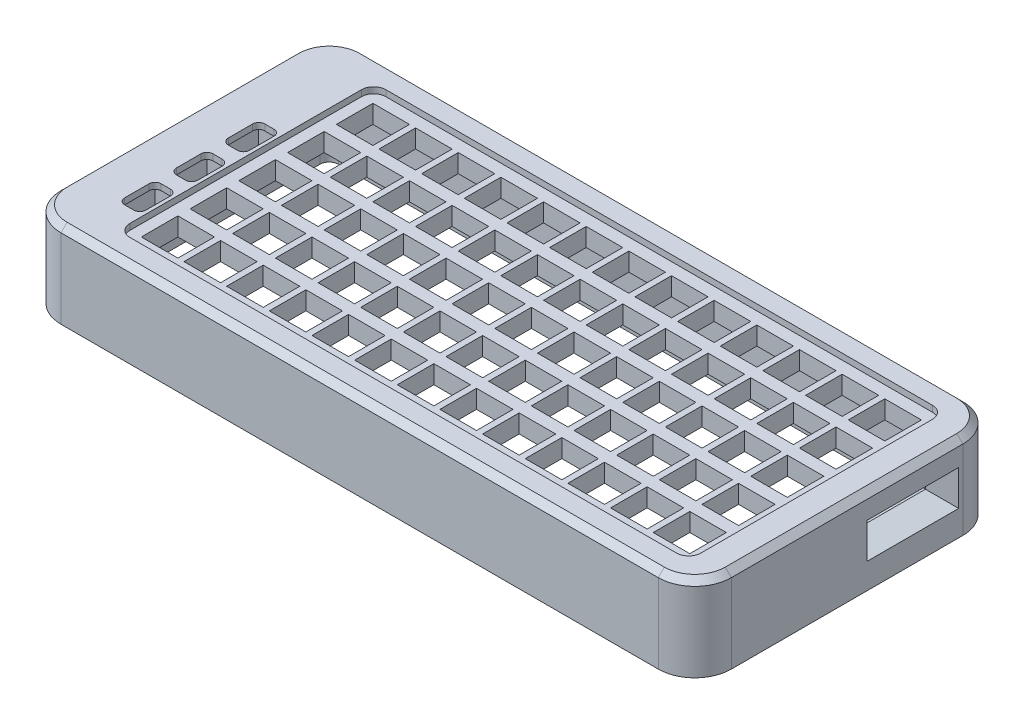
SolidWorks part; units mm, degrees
ref_plane "前视基准面" through (0, 0, 0) normal (0, 0, 1) x (1, 0, 0)
ref_plane "上视基准面" through (0, 0, 0) normal (0, 1, 0) x (1, 0, 0)
ref_plane "右视基准面" through (0, 0, 0) normal (1, 0, 0) x (0, 0, -1)
other "Configuration Table"
sketch "草图1" plane through (0, 0, 0) normal (0, 1, 0) x (1, 0, 0)
  line L1 (-55, -25) -> (55, -25)
  line L2 (-55, -25) -> (-55, 25)
  line L3 (-55, 25) -> (55, 25)
  line L4 (55, -25) -> (55, 25)
  line L5 (-55, -25) -> (55, 25) construction
  line L6 (-55, 25) -> (55, -25) construction
  point P0 (0, 0)
  dimension "D1" = 50
  dimension "D2" = 110
extrude "凸台-拉伸1" add sketch "草图1" along normal blind 3
sketch "草图2" plane through (0, 0, 0) normal (0, -1, 0) x (1, 0, 0)
  line L0 (46.3251, 14.2) -> (44.0251, 17.8) construction
  line L1 (48.1751, 11) -> (48.1751, 5)
  line L2 (48.1751, 19) -> (42.1751, 19)
  line L3 (48.1751, 19) -> (48.1751, 13)
  line L4 (48.1751, 13) -> (42.1751, 13)
  line L5 (42.1751, 19) -> (42.1751, 13)
  line L6 (48.1751, 19) -> (42.1751, 13) construction
  line L7 (48.1751, 13) -> (42.1751, 19) construction
  line L8 (48.1751, 5) -> (42.1751, 5)
  line L9 (42.1751, 11) -> (42.1751, 5)
  line L10 (48.1751, 11) -> (42.1751, 11)
  line L11 (48.1751, 3) -> (48.1751, -3)
  line L12 (48.1751, -3) -> (42.1751, -3)
  line L13 (42.1751, 3) -> (42.1751, -3)
  line L14 (48.1751, 3) -> (42.1751, 3)
  line L15 (48.1751, -5) -> (48.1751, -11)
  line L16 (48.1751, -11) -> (42.1751, -11)
  line L17 (42.1751, -5) -> (42.1751, -11)
  line L18 (48.1751, -5) -> (42.1751, -5)
  line L19 (48.1751, -13) -> (48.1751, -19)
  line L20 (48.1751, -19) -> (42.1751, -19)
  line L21 (42.1751, -13) -> (42.1751, -19)
  line L22 (48.1751, -13) -> (42.1751, -13)
  line L23 (41.1751, 11) -> (41.1751, 5)
  line L24 (41.1751, 5) -> (35.1751, 5)
  line L25 (35.1751, 11) -> (35.1751, 5)
  line L26 (41.1751, 11) -> (35.1751, 11)
  line L27 (41.1751, 3) -> (41.1751, -3)
  line L28 (41.1751, -3) -> (35.1751, -3)
  line L29 (35.1751, 3) -> (35.1751, -3)
  line L30 (41.1751, 3) -> (35.1751, 3)
  line L31 (41.1751, -5) -> (41.1751, -11)
  line L32 (41.1751, -11) -> (35.1751, -11)
  line L33 (35.1751, -5) -> (35.1751, -11)
  line L34 (41.1751, -5) -> (35.1751, -5)
  line L35 (41.1751, -13) -> (41.1751, -19)
  line L36 (41.1751, -19) -> (35.1751, -19)
  line L37 (35.1751, -13) -> (35.1751, -19)
  line L38 (41.1751, -13) -> (35.1751, -13)
  line L39 (34.1751, 11) -> (34.1751, 5)
  line L40 (34.1751, 5) -> (28.1751, 5)
  line L41 (28.1751, 11) -> (28.1751, 5)
  line L42 (34.1751, 11) -> (28.1751, 11)
  line L43 (34.1751, 3) -> (34.1751, -3)
  line L44 (34.1751, -3) -> (28.1751, -3)
  line L45 (28.1751, 3) -> (28.1751, -3)
  line L46 (34.1751, 3) -> (28.1751, 3)
  line L47 (34.1751, -5) -> (34.1751, -11)
  line L48 (34.1751, -11) -> (28.1751, -11)
  line L49 (28.1751, -5) -> (28.1751, -11)
  line L50 (34.1751, -5) -> (28.1751, -5)
  line L51 (34.1751, -13) -> (34.1751, -19)
  line L52 (34.1751, -19) -> (28.1751, -19)
  line L53 (28.1751, -13) -> (28.1751, -19)
  line L54 (34.1751, -13) -> (28.1751, -13)
  line L55 (27.1751, 11) -> (27.1751, 5)
  line L56 (27.1751, 5) -> (21.1751, 5)
  line L57 (21.1751, 11) -> (21.1751, 5)
  line L58 (27.1751, 11) -> (21.1751, 11)
  line L59 (27.1751, 3) -> (27.1751, -3)
  line L60 (27.1751, -3) -> (21.1751, -3)
  line L61 (21.1751, 3) -> (21.1751, -3)
  line L62 (27.1751, 3) -> (21.1751, 3)
  line L63 (27.1751, -5) -> (27.1751, -11)
  line L64 (27.1751, -11) -> (21.1751, -11)
  line L65 (21.1751, -5) -> (21.1751, -11)
  line L66 (27.1751, -5) -> (21.1751, -5)
  line L67 (27.1751, -13) -> (27.1751, -19)
  line L68 (27.1751, -19) -> (21.1751, -19)
  line L69 (21.1751, -13) -> (21.1751, -19)
  line L70 (27.1751, -13) -> (21.1751, -13)
  line L71 (20.1751, 11) -> (20.1751, 5)
  line L72 (20.1751, 5) -> (14.1751, 5)
  line L73 (14.1751, 11) -> (14.1751, 5)
  line L74 (20.1751, 11) -> (14.1751, 11)
  line L75 (20.1751, 3) -> (20.1751, -3)
  line L76 (20.1751, -3) -> (14.1751, -3)
  line L77 (14.1751, 3) -> (14.1751, -3)
  line L78 (20.1751, 3) -> (14.1751, 3)
  line L79 (20.1751, -5) -> (20.1751, -11)
  line L80 (20.1751, -11) -> (14.1751, -11)
  line L81 (14.1751, -5) -> (14.1751, -11)
  line L82 (20.1751, -5) -> (14.1751, -5)
  line L83 (20.1751, -13) -> (20.1751, -19)
  line L84 (20.1751, -19) -> (14.1751, -19)
  line L85 (14.1751, -13) -> (14.1751, -19)
  line L86 (20.1751, -13) -> (14.1751, -13)
  line L87 (13.1751, 11) -> (13.1751, 5)
  line L88 (13.1751, 5) -> (7.1751, 5)
  line L89 (7.1751, 11) -> (7.1751, 5)
  line L90 (13.1751, 11) -> (7.1751, 11)
  line L91 (13.1751, 3) -> (13.1751, -3)
  line L92 (13.1751, -3) -> (7.1751, -3)
  line L93 (7.1751, 3) -> (7.1751, -3)
  line L94 (13.1751, 3) -> (7.1751, 3)
  line L95 (13.1751, -5) -> (13.1751, -11)
  line L96 (13.1751, -11) -> (7.1751, -11)
  line L97 (7.1751, -5) -> (7.1751, -11)
  line L98 (13.1751, -5) -> (7.1751, -5)
  line L99 (13.1751, -13) -> (13.1751, -19)
  line L100 (13.1751, -19) -> (7.1751, -19)
  line L101 (7.1751, -13) -> (7.1751, -19)
  line L102 (13.1751, -13) -> (7.1751, -13)
  line L103 (6.1751, 11) -> (6.1751, 5)
  line L104 (6.1751, 5) -> (0.1751, 5)
  line L105 (0.1751, 11) -> (0.1751, 5)
  line L106 (6.1751, 11) -> (0.1751, 11)
  line L107 (6.1751, 3) -> (6.1751, -3)
  line L108 (6.1751, -3) -> (0.1751, -3)
  line L109 (0.1751, 3) -> (0.1751, -3)
  line L110 (6.1751, 3) -> (0.1751, 3)
  line L111 (6.1751, -5) -> (6.1751, -11)
  line L112 (6.1751, -11) -> (0.1751, -11)
  line L113 (0.1751, -5) -> (0.1751, -11)
  line L114 (6.1751, -5) -> (0.1751, -5)
  line L115 (6.1751, -13) -> (6.1751, -19)
  line L116 (6.1751, -19) -> (0.1751, -19)
  line L117 (0.1751, -13) -> (0.1751, -19)
  line L118 (6.1751, -13) -> (0.1751, -13)
  line L119 (-0.8249, 11) -> (-0.8249, 5)
  line L120 (-0.8249, 5) -> (-6.8249, 5)
  line L121 (-6.8249, 11) -> (-6.8249, 5)
  line L122 (-0.8249, 11) -> (-6.8249, 11)
  line L123 (-0.8249, 3) -> (-0.8249, -3)
  line L124 (-0.8249, -3) -> (-6.8249, -3)
  line L125 (-6.8249, 3) -> (-6.8249, -3)
  line L126 (-0.8249, 3) -> (-6.8249, 3)
  line L127 (-0.8249, -5) -> (-0.8249, -11)
  line L128 (-0.8249, -11) -> (-6.8249, -11)
  line L129 (-6.8249, -5) -> (-6.8249, -11)
  line L130 (-0.8249, -5) -> (-6.8249, -5)
  line L131 (-0.8249, -13) -> (-0.8249, -19)
  line L132 (-0.8249, -19) -> (-6.8249, -19)
  line L133 (-6.8249, -13) -> (-6.8249, -19)
  line L134 (-0.8249, -13) -> (-6.8249, -13)
  line L135 (-7.8249, 11) -> (-7.8249, 5)
  line L136 (-7.8249, 5) -> (-13.8249, 5)
  line L137 (-13.8249, 11) -> (-13.8249, 5)
  line L138 (-7.8249, 11) -> (-13.8249, 11)
  line L139 (-7.8249, 3) -> (-7.8249, -3)
  line L140 (-7.8249, -3) -> (-13.8249, -3)
  line L141 (-13.8249, 3) -> (-13.8249, -3)
  line L142 (-7.8249, 3) -> (-13.8249, 3)
  line L143 (-7.8249, -5) -> (-7.8249, -11)
  line L144 (-7.8249, -11) -> (-13.8249, -11)
  line L145 (-13.8249, -5) -> (-13.8249, -11)
  line L146 (-7.8249, -5) -> (-13.8249, -5)
  line L147 (-7.8249, -13) -> (-7.8249, -19)
  line L148 (-7.8249, -19) -> (-13.8249, -19)
  line L149 (-13.8249, -13) -> (-13.8249, -19)
  line L150 (-7.8249, -13) -> (-13.8249, -13)
  line L151 (-14.8249, 11) -> (-14.8249, 5)
  line L152 (-14.8249, 5) -> (-20.8249, 5)
  line L153 (-20.8249, 11) -> (-20.8249, 5)
  line L154 (-14.8249, 11) -> (-20.8249, 11)
  line L155 (-14.8249, 3) -> (-14.8249, -3)
  line L156 (-14.8249, -3) -> (-20.8249, -3)
  line L157 (-20.8249, 3) -> (-20.8249, -3)
  line L158 (-14.8249, 3) -> (-20.8249, 3)
  line L159 (-14.8249, -5) -> (-14.8249, -11)
  line L160 (-14.8249, -11) -> (-20.8249, -11)
  line L161 (-20.8249, -5) -> (-20.8249, -11)
  line L162 (-14.8249, -5) -> (-20.8249, -5)
  line L163 (-14.8249, -13) -> (-14.8249, -19)
  line L164 (-14.8249, -19) -> (-20.8249, -19)
  line L165 (-20.8249, -13) -> (-20.8249, -19)
  line L166 (-14.8249, -13) -> (-20.8249, -13)
  line L167 (-21.8249, 11) -> (-21.8249, 5)
  line L168 (-21.8249, 5) -> (-27.8249, 5)
  line L169 (-27.8249, 11) -> (-27.8249, 5)
  line L170 (-21.8249, 11) -> (-27.8249, 11)
  line L171 (-21.8249, 3) -> (-21.8249, -3)
  line L172 (-21.8249, -3) -> (-27.8249, -3)
  line L173 (-27.8249, 3) -> (-27.8249, -3)
  line L174 (-21.8249, 3) -> (-27.8249, 3)
  line L175 (-21.8249, -5) -> (-21.8249, -11)
  line L176 (-21.8249, -11) -> (-27.8249, -11)
  line L177 (-27.8249, -5) -> (-27.8249, -11)
  line L178 (-21.8249, -5) -> (-27.8249, -5)
  line L179 (-21.8249, -13) -> (-21.8249, -19)
  line L180 (-21.8249, -19) -> (-27.8249, -19)
  line L181 (-27.8249, -13) -> (-27.8249, -19)
  line L182 (-21.8249, -13) -> (-27.8249, -13)
  line L183 (-28.8249, 11) -> (-28.8249, 5)
  line L184 (-28.8249, 5) -> (-34.8249, 5)
  line L185 (-34.8249, 11) -> (-34.8249, 5)
  line L186 (-28.8249, 11) -> (-34.8249, 11)
  line L187 (-28.8249, 3) -> (-28.8249, -3)
  line L188 (-28.8249, -3) -> (-34.8249, -3)
  line L189 (-34.8249, 3) -> (-34.8249, -3)
  line L190 (-28.8249, 3) -> (-34.8249, 3)
  line L191 (-28.8249, -5) -> (-28.8249, -11)
  line L192 (-28.8249, -11) -> (-34.8249, -11)
  line L193 (-34.8249, -5) -> (-34.8249, -11)
  line L194 (-28.8249, -5) -> (-34.8249, -5)
  line L195 (-28.8249, -13) -> (-28.8249, -19)
  line L196 (-28.8249, -19) -> (-34.8249, -19)
  line L197 (-34.8249, -13) -> (-34.8249, -19)
  line L198 (-28.8249, -13) -> (-34.8249, -13)
  line L199 (-35.8249, 11) -> (-35.8249, 5)
  line L200 (-35.8249, 5) -> (-41.8249, 5)
  line L201 (-41.8249, 11) -> (-41.8249, 5)
  line L202 (-35.8249, 11) -> (-41.8249, 11)
  line L203 (-35.8249, 3) -> (-35.8249, -3)
  line L204 (-35.8249, -3) -> (-41.8249, -3)
  line L205 (-41.8249, 3) -> (-41.8249, -3)
  line L206 (-35.8249, 3) -> (-41.8249, 3)
  line L207 (-35.8249, -5) -> (-35.8249, -11)
  line L208 (-35.8249, -11) -> (-41.8249, -11)
  line L209 (-41.8249, -5) -> (-41.8249, -11)
  line L210 (-35.8249, -5) -> (-41.8249, -5)
  line L211 (-35.8249, -13) -> (-35.8249, -19)
  line L212 (-35.8249, -19) -> (-41.8249, -19)
  line L213 (-41.8249, -13) -> (-41.8249, -19)
  line L214 (-35.8249, -13) -> (-41.8249, -13)
  line L215 (41.1751, 19) -> (41.1751, 13)
  line L216 (41.1751, 13) -> (35.1751, 13)
  line L217 (35.1751, 19) -> (35.1751, 13)
  line L218 (41.1751, 19) -> (35.1751, 19)
  line L219 (34.1751, 19) -> (34.1751, 13)
  line L220 (34.1751, 13) -> (28.1751, 13)
  line L221 (28.1751, 19) -> (28.1751, 13)
  line L222 (34.1751, 19) -> (28.1751, 19)
  line L223 (27.1751, 19) -> (27.1751, 13)
  line L224 (27.1751, 13) -> (21.1751, 13)
  line L225 (21.1751, 19) -> (21.1751, 13)
  line L226 (27.1751, 19) -> (21.1751, 19)
  line L227 (20.1751, 19) -> (20.1751, 13)
  line L228 (20.1751, 13) -> (14.1751, 13)
  line L229 (14.1751, 19) -> (14.1751, 13)
  line L230 (20.1751, 19) -> (14.1751, 19)
  line L231 (13.1751, 19) -> (13.1751, 13)
  line L232 (13.1751, 13) -> (7.1751, 13)
  line L233 (7.1751, 19) -> (7.1751, 13)
  line L234 (13.1751, 19) -> (7.1751, 19)
  line L235 (6.1751, 19) -> (6.1751, 13)
  line L236 (6.1751, 13) -> (0.1751, 13)
  line L237 (0.1751, 19) -> (0.1751, 13)
  line L238 (6.1751, 19) -> (0.1751, 19)
  line L239 (-0.8249, 19) -> (-0.8249, 13)
  line L240 (-0.8249, 13) -> (-6.8249, 13)
  line L241 (-6.8249, 19) -> (-6.8249, 13)
  line L242 (-0.8249, 19) -> (-6.8249, 19)
  line L243 (-7.8249, 19) -> (-7.8249, 13)
  line L244 (-7.8249, 13) -> (-13.8249, 13)
  line L245 (-13.8249, 19) -> (-13.8249, 13)
  line L246 (-7.8249, 19) -> (-13.8249, 19)
  line L247 (-14.8249, 19) -> (-14.8249, 13)
  line L248 (-14.8249, 13) -> (-20.8249, 13)
  line L249 (-20.8249, 19) -> (-20.8249, 13)
  line L250 (-14.8249, 19) -> (-20.8249, 19)
  line L251 (-21.8249, 19) -> (-21.8249, 13)
  line L252 (-21.8249, 13) -> (-27.8249, 13)
  line L253 (-27.8249, 19) -> (-27.8249, 13)
  line L254 (-21.8249, 19) -> (-27.8249, 19)
  line L255 (-28.8249, 19) -> (-28.8249, 13)
  line L256 (-28.8249, 13) -> (-34.8249, 13)
  line L257 (-34.8249, 19) -> (-34.8249, 13)
  line L258 (-28.8249, 19) -> (-34.8249, 19)
  line L259 (-35.8249, 19) -> (-35.8249, 13)
  line L260 (-35.8249, 13) -> (-41.8249, 13)
  line L261 (-41.8249, 19) -> (-41.8249, 13)
  line L262 (-35.8249, 19) -> (-41.8249, 19)
  point P2 (45.1751, 16)
  dimension "D1" = 6
  dimension "D2" = 6
  dimension "D3" = 5
  dimension "D4" = 13
extrude "切除-拉伸1" cut sketch "草图2" against normal blind 10
sketch "草图3" plane through (0, 3, 0) normal (0, 1, 0) x (1, 0, 0)
  line L0 (-55, 25) -> (-55, -25) construction
  line L1 (-55, 25) -> (55, 25)
  line L2 (-55, 25) -> (-55, -25)
  line L3 (-55, -25) -> (55, -25)
  line L4 (55, 25) -> (55, -25)
  line L5 (55, 25) -> (-55, 25) construction
  line L6 (55, -25) -> (55, 25) construction
  line L7 (-55, -25) -> (55, -25) construction
  line L9 (-43.7, 21) -> (50, 21)
  line L10 (-43.7, 21) -> (-43.7, -21)
  line L11 (-43.7, -21) -> (50, -21)
  line L12 (50, 21) -> (50, -21)
  dimension "D1" = 4
  dimension "D2" = 4
  dimension "D3" = 5
  dimension "D4" = 42
  dimension "D5" = 11.3
extrude "凸台-拉伸2" add sketch "草图3" along normal blind 1
fillet "圆角1" radius 6 4 edges at (-55, 2, -25) (-55, 2, 25) (55, 2, 25) (55, 2, -25)
sketch "草图4" plane through (0, 0, 0) normal (0, -1, 0) x (1, 0, 0)
  line L0 (-45.3973, -4.764) -> (-46.6251, -1.636) construction
  line L1 (-45.3973, 3.736) -> (-46.6251, 6.864) construction
  line L2 (-45.2612, -0.2) -> (-46.7612, -0.2)
  line L3 (-44.2612, -1.2) -> (-44.2612, -5.2)
  line L4 (-45.2612, -6.2) -> (-46.7612, -6.2)
  line L5 (-47.7612, -1.2) -> (-47.7612, -5.2)
  line L6 (-44.2612, -0.2) -> (-47.7612, -6.2) construction
  line L7 (-44.2612, -6.2) -> (-47.7612, -0.2) construction
  line L8 (-44.2612, 7.3) -> (-44.2612, 3.3)
  line L9 (-45.2612, 8.3) -> (-46.7612, 8.3)
  line L10 (-47.7612, 7.3) -> (-47.7612, 3.3)
  line L11 (-45.2612, 2.3) -> (-46.7612, 2.3)
  line L12 (-45.3973, 12.236) -> (-46.6251, 15.364) construction
  line L13 (-44.2612, 15.8) -> (-44.2612, 11.8)
  line L14 (-45.2612, 16.8) -> (-46.7612, 16.8)
  line L15 (-47.7612, 15.8) -> (-47.7612, 11.8)
  line L16 (-45.2612, 10.8) -> (-46.7612, 10.8)
  arc A0 (-46.7612, 16.8) -> (-47.7612, 15.8) centre (-46.7612, 15.8) ccw
  arc A1 (-44.2612, 11.8) -> (-45.2612, 10.8) centre (-45.2612, 11.8) cw
  arc A2 (-44.2612, 15.8) -> (-45.2612, 16.8) centre (-45.2612, 15.8) ccw
  arc A3 (-47.7612, 11.8) -> (-46.7612, 10.8) centre (-46.7612, 11.8) ccw
  arc A4 (-46.7612, 8.3) -> (-47.7612, 7.3) centre (-46.7612, 7.3) ccw
  arc A5 (-44.2612, 3.3) -> (-45.2612, 2.3) centre (-45.2612, 3.3) cw
  arc A6 (-44.2612, 7.3) -> (-45.2612, 8.3) centre (-45.2612, 7.3) ccw
  arc A7 (-47.7612, 3.3) -> (-46.7612, 2.3) centre (-46.7612, 3.3) ccw
  arc A8 (-46.7612, -0.2) -> (-47.7612, -1.2) centre (-46.7612, -1.2) ccw
  arc A9 (-44.2612, -5.2) -> (-45.2612, -6.2) centre (-45.2612, -5.2) cw
  arc A10 (-45.2612, -0.2) -> (-44.2612, -1.2) centre (-45.2612, -1.2) cw
  arc A11 (-46.7612, -6.2) -> (-47.7612, -5.2) centre (-46.7612, -5.2) cw
  point P2 (-46.0112, -3.2)
  dimension "D4" = 1
  dimension "D1" = 3.5
  dimension "D2" = 6
  dimension "D3" = 3
extrude "切除-拉伸2" cut sketch "草图4" against normal blind 6
sketch "草图5" plane through (0, 0, 0) normal (0, -1, 0) x (1, 0, 0)
  line L0 (-46.0112, -6.2) -> (-46.0112, -0.2) construction
  line L1 (-46.7612, -6.2) -> (-45.2612, -6.2) construction
  line L2 (-45.2612, -0.2) -> (-46.7612, -0.2) construction
  line L3 (-43.7612, 8.8) -> (-43.7612, 1.8)
  line L4 (-43.7612, 0.3) -> (-48.2612, 0.3)
  line L5 (-43.7612, 0.3) -> (-43.7612, -6.7)
  line L6 (-43.7612, -6.7) -> (-48.2612, -6.7)
  line L7 (-48.2612, 0.3) -> (-48.2612, -6.7)
  line L8 (-43.7612, 0.3) -> (-48.2612, -6.7) construction
  line L9 (-43.7612, -6.7) -> (-48.2612, 0.3) construction
  line L10 (-43.7612, 8.8) -> (-48.2612, 8.8)
  line L11 (-48.2612, 8.8) -> (-48.2612, 1.8)
  line L12 (-43.7612, 1.8) -> (-48.2612, 1.8)
  line L13 (-43.7612, 17.3) -> (-43.7612, 10.3)
  line L14 (-43.7612, 17.3) -> (-48.2612, 17.3)
  line L15 (-48.2612, 17.3) -> (-48.2612, 10.3)
  line L16 (-43.7612, 10.3) -> (-48.2612, 10.3)
  point P6 (-46.0112, -3.2)
  dimension "D1" = 7
  dimension "D2" = 4.5
  dimension "D3" = 3
extrude "切除-拉伸3" cut sketch "草图5" against normal blind 3
fillet "圆角2" radius 2 4 edges at (50, 3.5, 21) (50, 3.5, -21) (-43.7, 3.5, -21) (-43.7, 3.5, 21)
chamfer "倒角1" distance 1 angle 45 8 edges at (53.2426, 4, -23.2426) (0, 4, -25) (55, 4, 0) (-53.2426, 4, -23.2426) (53.2426, 4, 23.2426) (-55, 4, 0) (0, 4, 25) (-53.2426, 4, 23.2426)
sketch "草图6" plane through (0, 0, 0) normal (0, -1, 0) x (1, 0, 0)
  line L6 (-55, 19) -> (-55, -19)
  line L7 (-49, -25) -> (49, -25)
  line L8 (-55, 19) -> (-55, -19)
  line L9 (-49, -25) -> (49, -25)
  line L10 (55, 19) -> (55, -19)
  line L11 (55, 19) -> (55, -19)
  line L13 (50.5, 19) -> (50.5, -19)
  line L14 (49, 25) -> (-49, 25)
  line L15 (49, 25) -> (-49, 25)
  line L16 (49, 20.5) -> (-49, 20.5)
  line L17 (-50.5, 19) -> (-50.5, -19)
  line L18 (-49, -20.5) -> (49, -20.5)
  arc A8 (-55, -19) -> (-49, -25) centre (-49, -19) ccw
  arc A9 (49, -25) -> (55, -19) centre (49, -19) ccw
  arc A10 (-55, -19) -> (-49, -25) centre (-49, -19) ccw
  arc A11 (49, -25) -> (55, -19) centre (49, -19) ccw
  arc A14 (49, -20.5) -> (50.5, -19) centre (49, -19) ccw
  arc A15 (50.5, 19) -> (49, 20.5) centre (49, 19) ccw
  arc A16 (-49, 25) -> (-55, 19) centre (-49, 19) ccw
  arc A17 (55, 19) -> (49, 25) centre (49, 19) ccw
  arc A18 (-49, 25) -> (-55, 19) centre (-49, 19) ccw
  arc A19 (55, 19) -> (49, 25) centre (49, 19) ccw
  arc A20 (-49, 20.5) -> (-50.5, 19) centre (-49, 19) ccw
  arc A21 (-50.5, -19) -> (-49, -20.5) centre (-49, -19) ccw
  dimension "D1" = 0
  dimension "D2" = 0
  dimension "D3" = 0
  dimension "D4" = 4.5
extrude "凸台-拉伸3" add sketch "草图6" along normal blind 10
sketch "草图8" plane through (-50.5, 0, 0) normal (1, 0, 0) x (0, 0, -1)
  line L0 (15.184, -3.2801) -> (8.184, -3.2801) construction
  line L1 (14.6841, -3.2801) -> (8.6839, -3.2801) construction
  line L2 (14.6841, -5.0285) -> (8.6839, -5.0285)
  line L3 (14.6841, -1.5316) -> (8.6839, -1.5316)
  arc A0 (14.6841, -5.0285) -> (14.6841, -1.5316) centre (14.6841, -3.2801) ccw
  arc A1 (8.6839, -1.5316) -> (8.6839, -5.0285) centre (8.6839, -3.2801) ccw
  point P4 (11.684, -3.2801)
  point P9 (8.6839, -3.2801)
extrude "切除-拉伸4" cut sketch "草图8" against normal blind 7
sketch "草图9" plane through (-55, 0, 0) normal (-1, 0, 0) x (0, 0, 1)
  line L0 (-15.0883, -3.2801) -> (-8.2797, -3.2801) construction
  line L1 (-15.0883, -0.0301) -> (-8.2797, -0.0301)
  line L4 (-15.0883, -6.5301) -> (-8.2797, -6.5301)
  line L5 (-14.6841, -1.5316) -> (-8.6839, -1.5316) construction
  arc A6 (-15.0883, -0.0301) -> (-15.0883, -6.5301) centre (-15.0883, -3.2801) ccw
  arc A7 (-8.2797, -6.5301) -> (-8.2797, -0.0301) centre (-8.2797, -3.2801) ccw
  point P2 (-11.684, -3.2801)
  point P7 (-7.7917, -3.3156)
  point P8 (-11.684, -3.2801)
  point P11 (-8.2784, -3.2669)
  dimension "D3" = 3.25
  dimension "D1" = 6.5
  dimension "D2" = 1.5015
extrude "切除-拉伸5" cut sketch "草图9" against normal blind 3.5
sketch "草图10" plane through (50.5, 0, 0) normal (-1, 0, 0) x (0, 0, 1)
  line L1 (-4.7442, -1.4441) -> (-16.8485, -1.4441)
  line L2 (-4.7442, -1.4441) -> (-4.7442, -4.3565)
  line L3 (-4.7442, -4.3565) -> (-16.8485, -4.3565)
  line L4 (-16.8485, -1.4441) -> (-16.8485, -4.3565)
extrude "切除-拉伸6" cut sketch "草图10" against normal blind 6.5
chamfer "倒角2" distance 4 angle 20 1 edges at (55, -1.4441, -10.7963) first distance on face at (52.75, -1.4441, -10.7963)
chamfer "倒角3" distance 4 angle 20 1 edges at (55, -4.3565, -10.7963) first distance on face at (52.75, -4.3565, -10.7963)
chamfer "倒角4" distance 4 angle 20 1 edges at (55, -2.9003, -4.7442) first distance on face at (52.1667, -2.9003, -4.7442)
chamfer "倒角5" distance 4 angle 20 1 edges at (55, -2.9003, -16.8485) first distance on face at (52.1667, -2.9003, -16.8485)
sketch "草图11" plane through (0, -10, 0) normal (0, -1, 0) x (1, 0, 0)
  line L0 (-49, -25) -> (49, -25) construction
  line L2 (0, 0) -> (50000, 0) construction
  circle A0 centre (0, -22.7) radius 1.55
  circle A1 centre (20, -22.7) radius 1.55
  circle A2 centre (40, -22.7) radius 1.55
  circle A3 centre (-20, -22.7) radius 1.55
  circle A4 centre (-40, -22.7) radius 1.55
  circle A5 centre (-40, 22.7) radius 1.55
  circle A6 centre (-20, 22.7) radius 1.55
  circle A7 centre (40, 22.7) radius 1.55
  circle A8 centre (20, 22.7) radius 1.55
  circle A9 centre (0, 22.7) radius 1.55
  dimension "D1" = 3.1
  dimension "D3" = 3
  dimension "D2" = 2.3
  dimension "D4" = 3
extrude "切除-拉伸7" cut sketch "草图11" against normal blind 2
